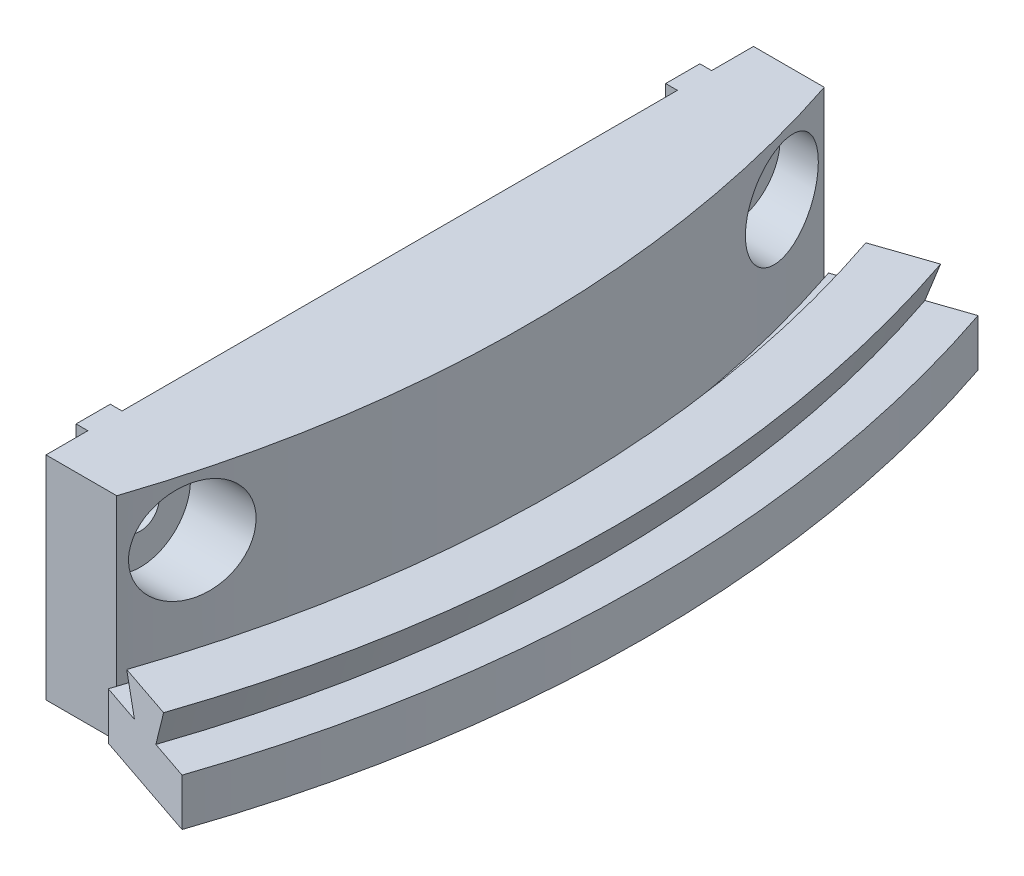
SolidWorks part; units mm, degrees
ref_plane "Front Plane" through (0, 0, 0) normal (0, 0, 1) x (1, 0, 0)
ref_plane "Top Plane" through (0, 0, 0) normal (0, 1, 0) x (1, 0, 0)
ref_plane "Right Plane" through (0, 0, 0) normal (1, 0, 0) x (0, 0, -1)
ref_axis "Axis1" through (0, -0.2847, 0) along (0, 1, 0)
sketch "Sketch1" plane through (0, 0, 0) normal (0, 0, 1) x (1, 0, 0)
  line L0 (105, 0) -> (105, 4)
  line L1 (105, 4) -> (101.45, 4)
  line L3 (98.55, 4) -> (97.5, 7)
  line L5 (98.55, 4) -> (95, 4)
  line L6 (95, 4) -> (95, 0)
  line L7 (95, 0) -> (105, 0)
  line L8 (97.5, 7) -> (102.5, 7)
  line L9 (102.5, 7) -> (101.45, 4)
  point P2 (97.9725, 8)
  point P5 (100.8185, 4.7754)
  point P9 (100, 0)
  point P10 (101.5465, 4)
  point P14 (0, 0)
  dimension "D1" = 4
  dimension "D2" = 10
  dimension "D3" = 3.55
  dimension "D4" = 100
  dimension "D5" = 5
  dimension "D7" = 3
revolve "Main" add sketch "Sketch1" angle 37.5 mid plane about axis through (0, -0.2847, 0) along (0, 1, 0)
sketch "Sketch2" plane through (0, 0, 0) normal (0, -1, 0) x (-1, 0, 0)
  line L1 (-90.1388, -30) -> (-84.1388, -30)
  line L2 (-89.9584, -30.5367) -> (-89.9584, 30.5367) construction
  line L4 (0, 0) -> (-500, 169.7271) construction
  line L5 (0, 0) -> (-500, -169.7271) construction
  line L6 (-99.4277, 33.7511) -> (-96.0661, 32.61) construction
  line L7 (-89.9584, -30.5367) -> (-99.4277, -33.7511) construction
  line L8 (-500, 169.7271) -> (-500, -169.7271) construction
  line L10 (-84.1388, -30) -> (-84.1388, 30)
  line L11 (-84.1388, 30) -> (-90.1388, 30)
  arc A0 (-90.1388, -30) -> (-90.1388, 30) centre (0, 0) cw
  arc A3 (-89.9584, 30.5367) -> (-89.9584, -30.5367) centre (0, 0) ccw construction
  point P1 (-90.1388, -27.638)
  point P4 (0, 0)
  point P7 (0, 0)
  point P26 (-84.1388, 0)
  dimension "D1" = 60
  dimension "D2" = 6
  dimension "D4" = 61.0735
  dimension "D5" = 500
  dimension "D6" = 339.4543
extrude "Support" add sketch "Sketch2" against normal blind 18
sketch "Sketch3" plane through (0, 18, 0) normal (0, 1, 0) x (1, 0, 0)
  circle A0 centre (62.5378, 0) radius 50 construction
  dimension "D4" = 100
sketch "Sketch6" plane through (0, 0, 0) normal (0, 1, 0) x (1, 0, 0)
  line L0 (90.1388, -30) -> (84.1388, -30) construction
  line L1 (83.1388, -23.55) -> (84.1388, -23.55)
  line L2 (83.1388, -23.55) -> (83.1388, -26.45)
  line L3 (83.1388, -26.45) -> (84.1388, -26.45)
  line L4 (84.1388, -23.55) -> (84.1388, -26.45)
  line L6 (83.1388, 26.45) -> (84.1388, 26.45)
  line L7 (83.1388, 26.45) -> (83.1388, 23.55)
  line L8 (83.1388, 23.55) -> (84.1388, 23.55)
  line L9 (84.1388, 26.45) -> (84.1388, 23.55)
  line L11 (84.1388, -30) -> (84.1388, 30) construction
  line L12 (84.1388, 30) -> (90.1388, 30) construction
  dimension "D1" = 3.55
  dimension "D2" = 2.9
  dimension "D3" = 1
  dimension "D4" = 3.55
extrude "MakerBeamSupport" add sketch "Sketch6" along normal up to surface (18 mm away) up to face at (88.3541, 18, 0)
sketch "Sketch7" plane through (83.1388, 0, 0) normal (1, 0, 0) x (0, 0, -1)
  line L3 (30, 18) -> (30, 0) construction
  line L4 (-30, 18) -> (-30, 0) construction
  line L5 (50, 18) -> (-50, 18) construction
  circle A0 centre (-25, 13) radius 1.6
  circle A1 centre (25, 13) radius 1.6
  point P8 (0, 0)
  dimension "D1" = 3.2
  dimension "D2" = 5
  dimension "D3" = 5
  dimension "D4" = 5
extrude "HolesMakerBeam" cut sketch "Sketch7" along normal through all
ref_plane "Plane1" through (87.1388, 0, 0) normal (-1, 0, 0) x (0, 0, 1)
sketch "Sketch8" plane through (87.1388, 0, 0) normal (-1, 0, 0) x (0, 0, 1)
  circle A0 centre (25, 13) radius 4.25
  circle A1 centre (-25, 13) radius 4.25
  dimension "D1" = 8.5
  dimension "D2" = 8.5
extrude "Cut-Extrude1" cut sketch "Sketch8" against normal blind 7
